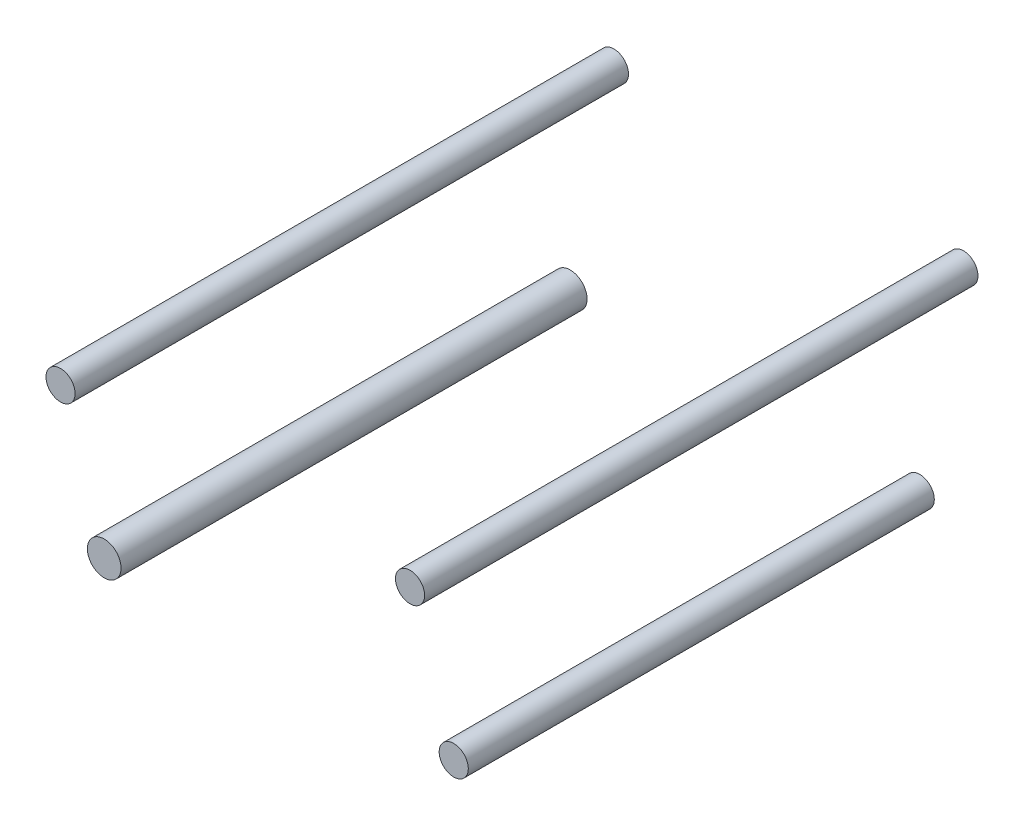
SolidWorks part; units mm, degrees
ref_plane "Front Plane" through (0, 0, 0) normal (0, 0, 1) x (1, 0, 0)
ref_plane "Top Plane" through (0, 0, 0) normal (0, 1, 0) x (1, 0, 0)
ref_plane "Right Plane" through (0, 0, 0) normal (1, 0, 0) x (0, 0, -1)
sketch "Sketch1" plane through (0, 0, 0) normal (0, 0, 1) x (1, 0, 0)
  line L1 (-152.4, 74.93) -> (152.4, 74.93) construction
  line L2 (-152.4, 74.93) -> (-152.4, -74.93) construction
  line L3 (-152.4, -74.93) -> (152.4, -74.93) construction
  line L4 (152.4, 74.93) -> (152.4, -74.93) construction
  line L5 (-152.4, 74.93) -> (152.4, -74.93) construction
  line L6 (-152.4, -74.93) -> (152.4, 74.93) construction
  circle A0 centre (-152.4, 74.93) radius 12.7
  circle A1 centre (152.4, 74.93) radius 12.7
  circle A2 centre (152.4, -74.93) radius 12.7
  circle A3 centre (-152.4, -74.93) radius 14.6943
  point P0 (0, 0)
  dimension "D3" = 25.4
  dimension "D1" = 149.86
  dimension "D2" = 304.8
extrude "Boss-Extrude1" add sketch "Sketch1" along normal blind 203.2 and the other way blind 203.2 contours A2 | A3
extrude "Boss-Extrude2" add sketch "Sketch1<3>" along normal blind 241.3 and the other way blind 241.3 separate body contours A1 | A0
sketch "Sketch1<3>" plane through (0, 0, 0) normal (0, 0, 1) x (1, 0, 0) same geometry as "Sketch1"
